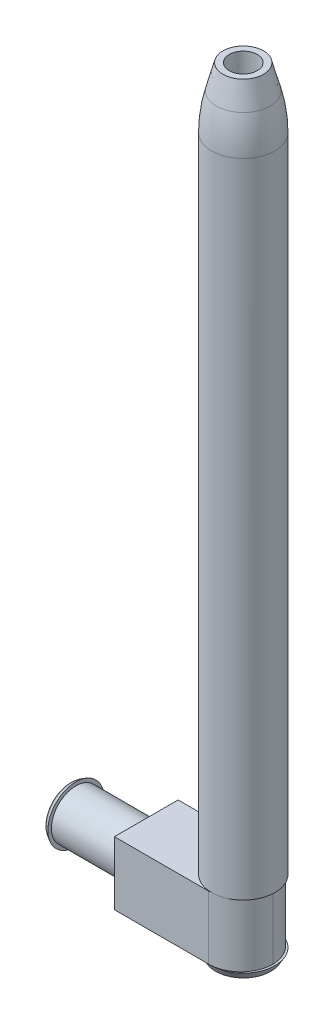
SolidWorks part; units mm, degrees
ref_plane "Front Plane" through (0, 0, 0) normal (0, 0, 1) x (1, 0, 0)
ref_plane "Top Plane" through (0, 0, 0) normal (0, 1, 0) x (1, 0, 0)
ref_plane "Right Plane" through (0, 0, 0) normal (1, 0, 0) x (0, 0, -1)
sketch "Sketch2" plane through (0, 0, 0) normal (1, 0, 0) x (0, 0, -1)
  circle A0 centre (0, 0) radius 4.445
  dimension "D1" = 8.89
extrude "Boss-Extrude1" add sketch "Sketch2" along normal mid plane 12.7
sketch "Sketch3" plane through (-6.35, 0, 0) normal (-1, 0, 0) x (0, 0, 1)
  circle A0 centre (0, 0) radius 5.08
  dimension "D1" = 10.16
extrude "Boss-Extrude2" add sketch "Sketch3" along normal blind 1.27 draft 30
fillet "Fillet1" radius 1.27 1 edges at (-7.62, 0, 4.3468)
ref_plane "Plane1" through (1.27, 0, 0) normal (1, 0, 0) x (0, 0, -1)
sketch "Sketch5" plane through (6.35, 0, 0) normal (1, 0, 0) x (0, 0, -1)
  line L1 (-5.7531, -5.715) -> (5.7531, -5.715)
  line L2 (-5.7531, -5.715) -> (-5.7531, 5.715)
  line L3 (-5.7531, 5.715) -> (5.7531, 5.715)
  line L4 (5.7531, -5.715) -> (5.7531, 5.715)
  line L5 (-5.7531, -5.715) -> (5.7531, 5.715) construction
  line L6 (-5.7531, 5.715) -> (5.7531, -5.715) construction
  point P0 (0, 0)
  dimension "D1" = 11.43
  dimension "D2" = 11.5062
extrude "Boss-Extrude4" add sketch "Sketch5" along normal blind 22.86
sketch "Sketch6" plane through (0, 5.715, 0) normal (0, 1, 0) x (1, 0, 0)
  line L0 (6.35, 0) -> (21.336, 0) construction
  line L3 (6.35, 5.7531) -> (6.35, -5.7531) construction
  circle A0 centre (23.876, 0) radius 2.54
  dimension "D2" = 5.08
  dimension "D1" = 14.986
extrude "Cut-Extrude1" cut sketch "Sketch6" against normal up to next
fillet "Fillet2" radius 5.842 2 edges at (29.21, 0, -5.7531) (29.21, 0, 5.7531)
sketch "Sketch7" plane through (0, -5.715, 0) normal (0, -1, 0) x (1, 0, 0)
  circle A0 centre (23.876, 0) radius 5.715
  circle A1 centre (23.876, 0) radius 2.54 construction
  dimension "D1" = 11.43
extrude "Boss-Extrude5" add sketch "Sketch7" along normal blind 1.27 draft 30
sketch "Sketch8" plane through (0, 5.715, 0) normal (0, 1, 0) x (1, 0, 0)
  circle A0 centre (23.876, 0) radius 5.715
  arc A1 (24.0592, -5.7121) -> (24.0592, 5.7121) centre (23.876, 0) ccw construction
  circle A2 centre (23.876, 0) radius 2.54
  circle A3 centre (23.876, 0) radius 2.54 construction
extrude "Boss-Extrude6" add sketch "Sketch8" along normal blind 127
chamfer "Chamfer1" distance 7.62 angle 15 1 edges at (23.876, 132.715, 5.715) first distance on face at (23.876, 132.715, 5.715)
fillet "Fillet3" radius 25.4 1 edges at (23.876, 125.095, 5.715)
